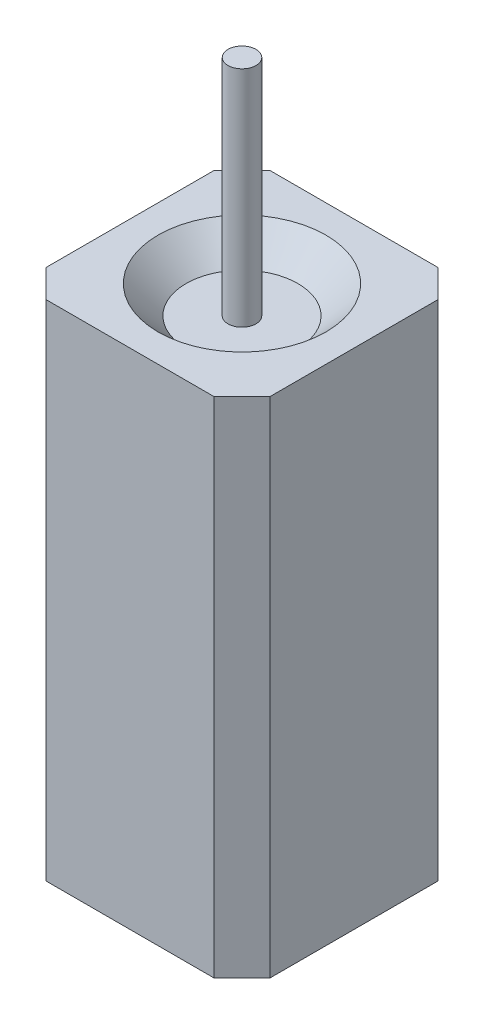
SolidWorks part; units mm, degrees
ref_plane "Front Plane" through (0, 0, 0) normal (0, 0, 1) x (1, 0, 0)
ref_plane "Top Plane" through (0, 0, 0) normal (0, 1, 0) x (1, 0, 0)
ref_plane "Right Plane" through (0, 0, 0) normal (1, 0, 0) x (0, 0, -1)
sketch "Sketch1" plane through (0, 0, 0) normal (0, 1, 0) x (1, 0, 0)
  line L1 (-25.4, -25.4) -> (25.4, -25.4)
  line L2 (-25.4, -25.4) -> (-25.4, 25.4)
  line L3 (-25.4, 25.4) -> (25.4, 25.4)
  line L4 (25.4, -25.4) -> (25.4, 25.4)
  line L5 (-25.4, -25.4) -> (25.4, 25.4) construction
  line L6 (-25.4, 25.4) -> (25.4, -25.4) construction
  point P0 (0, 0)
  dimension "D1" = 50.8
  dimension "D2" = 50.8
extrude "Boss-Extrude1" add sketch "Sketch1" along normal blind 114.3
sketch "Sketch2" plane through (0, 114.3, 0) normal (0, 1, 0) x (1, 0, 0)
  circle A0 centre (0, 0) radius 12.7
  dimension "D1" = 25.4
extrude "Cut-Extrude1" cut sketch "Sketch2" against normal blind 6.35
chamfer "Chamfer1" distance 6.35 angle 45 4 edges at (25.4, 57.15, 25.4) (-25.4, 57.15, 25.4) (-25.4, 57.15, -25.4) (25.4, 57.15, -25.4)
sketch "Sketch3" plane through (0, 107.95, 0) normal (0, 1, 0) x (1, 0, 0)
  circle A0 centre (0, 0) radius 3.175
  dimension "D1" = 6.35
extrude "Boss-Extrude2" add sketch "Sketch3" along normal blind 50.8
chamfer "Chamfer2" distance 6.35 angle 45 1 edges at (0, 114.3, 12.7)
